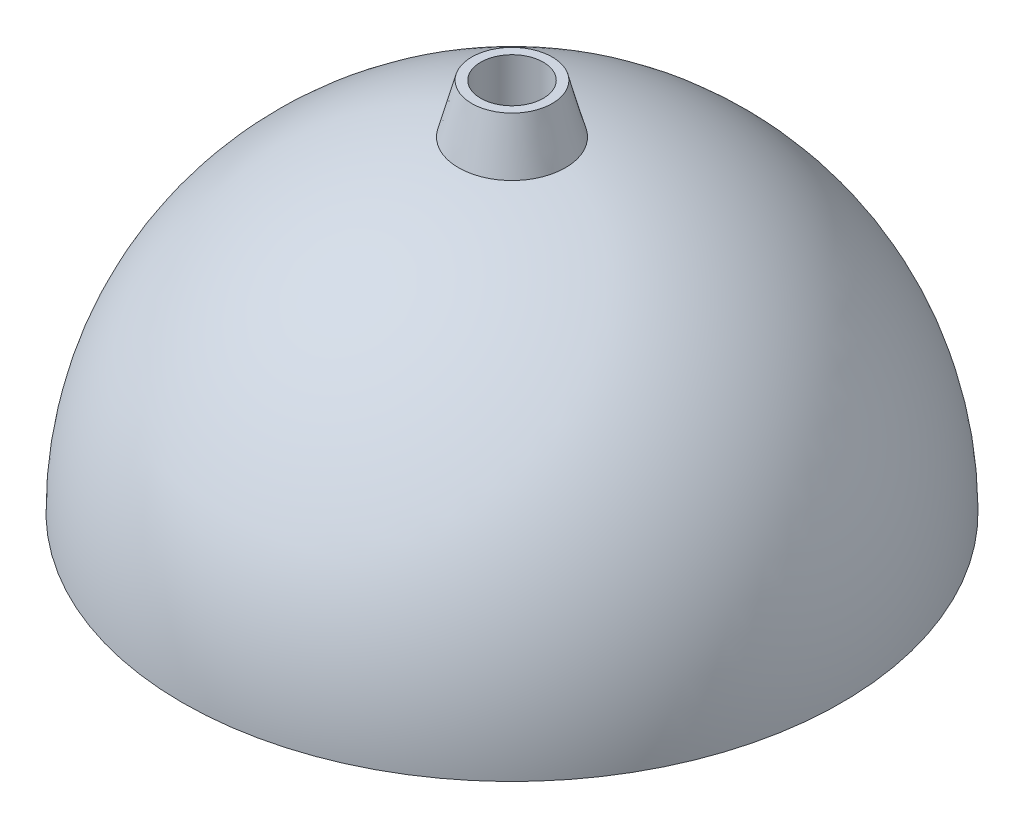
SolidWorks part; units mm, degrees
ref_plane "Front Plane" through (0, 0, 0) normal (0, 0, 1) x (1, 0, 0)
ref_plane "Top Plane" through (0, 0, 0) normal (0, 1, 0) x (1, 0, 0)
ref_plane "Right Plane" through (0, 0, 0) normal (1, 0, 0) x (0, 0, -1)
sketch "Sketch2" plane through (0, 0, 0) normal (0, 0, 1) x (1, 0, 0)
  line L0 (0, 73.66) -> (0, 0)
  line L1 (0, 0) -> (73.66, 0)
  arc A0 (73.66, 0) -> (0, 73.66) centre (0, 0) ccw
  dimension "D1" = 73.66
revolve "Dome" add sketch "Sketch2" angle 360 about L0
sketch "Sketch3" plane through (0, 0, 0) normal (0, -1, 0) x (1, 0, 0)
  circle A0 centre (0, 0) radius 50.8
  dimension "D1" = 101.6
extrude "Cut-Extrude1" cut sketch "Sketch3" against normal blind 35
sketch "Sketch4" plane through (0, 0, 0) normal (0, 0, 1) x (1, 0, 0)
  line L0 (-50.8, 0) -> (50.8, 0) construction
  line L1 (-50.8, 0) -> (50.8, 0)
  line L2 (-50.8, 0) -> (-50.8, 5)
  line L3 (-50.8, 5) -> (-62.2715, 33.393)
  line L4 (0, 0) -> (0, 70.66)
  line L5 (-50.8, 0) -> (0, 0)
  line L6 (-50.8, 0) -> (50.8, 0)
  circle A0 centre (0, 0) radius 70.66
  arc A1 (73.66, 0) -> (-73.66, 0) centre (0, 0) ccw construction
  dimension "D1" = 3
  dimension "D2" = 22
  dimension "D3" = 5
revolve "Wall Shape" cut sketch "Sketch4" angle 360 about L4 region at (-26.3163, 32.0925, 0)
fillet "Fillet1" radius 15 1 edges at (0, 33.393, -62.2715)
ref_plane "Plane1" through (0, -8, 0) normal (0, 1, 0) x (1, 0, 0)
sketch "Sketch5" plane through (0, -8, 0) normal (0, 1, 0) x (1, 0, 0)
  circle A0 centre (0, 0) radius 7
  dimension "D1" = 14
extrude "GSM Antenna" cut sketch "Sketch5" along normal through all
sketch "Sketch6" plane through (0, -8, 0) normal (0, 1, 0) x (1, 0, 0)
  circle A0 centre (0, -23.0752) radius 7
  dimension "D1" = 14
extrude "GPS Antenna" [suppressed] cut sketch "Sketch6" along normal through all
ref_axis "Axis1" through (-81.026, 0, 0) along (1, 0, 0)
ref_plane "Plane2" through (0, 0, 0) normal (0, -0.891, 0.454) x (1, 0, 0)
sketch "Sketch7" plane through (0, 0, 0) normal (0, -0.891, 0.454) x (1, 0, 0)
  circle A0 centre (0, 2) radius 12.7
  dimension "D1" = 25.4
  dimension "D2" = 2
extrude "Pressure Vent" [suppressed] cut sketch "Sketch7" against normal through all contours A0
sketch "Sketch9" plane through (0, 0, 0) normal (0, -1, 0) x (-1, 0, 0)
  circle A0 centre (0, -67.5) radius 1.75
  circle A1 centre (0, 0) radius 67.5
  dimension "D1" = 135
  dimension "D2" = 3.5
extrude "Cut-Extrude6" cut sketch "Sketch9" against normal blind 10 contours A0
sketch "Sketch10" plane through (0, 10, 0) normal (0, -1, 0) x (1, 0, 0)
  circle A0 centre (0, 67.5) radius 3.25
  dimension "D1" = 6.5
extrude "Bolt CounterBore" [suppressed] cut sketch "Sketch10" against normal through all
chamfer "Chamfer2" [suppressed] distance 2.5 angle 45
pattern_circular "CirPattern1" count 10 over 360 about axis through (0, 35, 0) along (0, -1, 0) of "Cut-Extrude6", "Bolt CounterBore"
ref_plane "Plane3" through (0, 65.6315, -33.4409) normal (0, 0.891, -0.454) x (-1, 0, 0)
ref_plane "Plane4" through (0, 67.4136, -34.3489) normal (0, 0.891, -0.454) x (-1, 0, 0)
sketch "Sketch12" [suppressed] plane through (0, 67.4136, -34.3489) normal (0, 0.891, -0.454) x (-1, 0, 0)
  circle A0 centre (0, 2) radius 19.5
  circle A1 centre (0, 2) radius 12.7
  dimension "D1" = 39
extrude "Cut-Extrude8" [suppressed] cut sketch "Sketch12" against normal blind 7 contours A0
ref_plane "Plane5" through (0, 73.66, 0) normal (0, 1, 0) x (1, 0, 0)
ref_plane "Plane6" through (0, 83.66, 0) normal (0, 1, 0) x (1, 0, 0)
sketch "Sketch13" plane through (0, 83.66, 0) normal (0, 1, 0) x (1, 0, 0)
  circle A0 centre (0, 0) radius 7
  circle A1 centre (0, 0) radius 9
  dimension "D1" = 2
extrude "Boss-Extrude2" add sketch "Sketch13" against normal up to surface (10.3334 mm away) up to face at (0, 0, 73.66)
draft "Draft2" type of draft neutral plane draft angle 15 faces to draft 1 face at (0, 83.66, 9) neutral plane through (0, 83.66, 0) neutral plane normal (0, 1, 0) parameters "D1"=15
